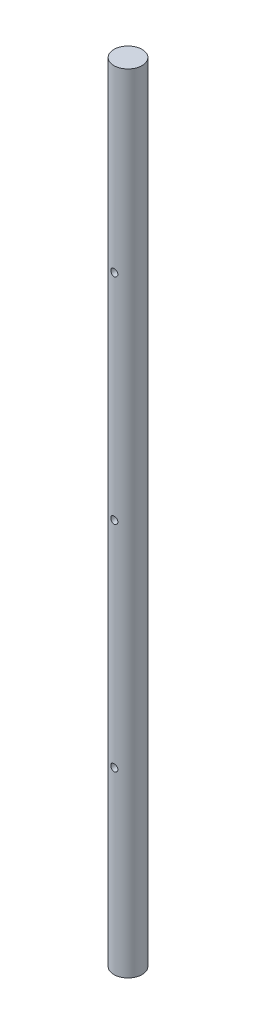
SolidWorks part; units mm, degrees
ref_plane "Plan de face" through (0, 0, 0) normal (0, 0, 1) x (1, 0, 0)
ref_plane "Plan de dessus" through (0, 0, 0) normal (0, 1, 0) x (1, 0, 0)
ref_plane "Plan de droite" through (0, 0, 0) normal (1, 0, 0) x (0, 0, -1)
sketch "Esquisse1" plane through (0, 0, 0) normal (0, 1, 0) x (1, 0, 0)
  circle A0 centre (0, 0) radius 5
  dimension "D1" = 10
extrude "Boss.-Extru.1" add sketch "Esquisse1" along normal blind 280
sketch "Sketch1" plane through (0, 0, 0) normal (0, 0, 1) x (1, 0, 0)
  line L0 (5, 0) -> (5, 280) construction
  line L1 (-5, 0) -> (5, 0) construction
  line L2 (-5, 280) -> (-5, 0) construction
  line L3 (5, 280) -> (-5, 280) construction
  circle A0 centre (0, 216.25) radius 1.25
  circle A1 centre (0, 140) radius 1.25
  circle A2 centre (0, 63.75) radius 1.25
  dimension "D1" = 2.5
  dimension "D6" = 2.5
  dimension "D7" = 2.5
  dimension "D2" = 63.75
  dimension "D3" = 5
  dimension "D4" = 140
  dimension "D5" = 5
  dimension "D8" = 63.75
  dimension "D9" = 5
extrude "Cut-Extrude1" cut sketch "Sketch1" against normal blind 10 and the other way blind 10
sketch "Sketch2" plane through (0, 0, 0) normal (0, 1, 0) x (1, 0, 0)
